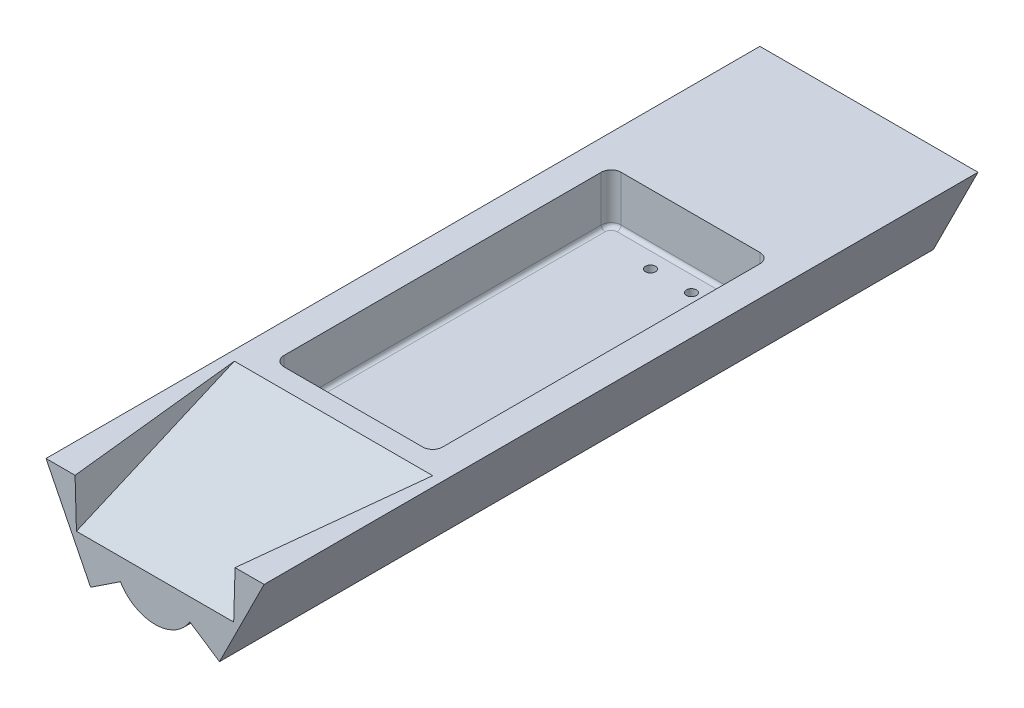
SolidWorks part; units mm, degrees
ref_plane "Front Plane" through (0, 0, 0) normal (0, 0, 1) x (1, 0, 0)
ref_plane "Top Plane" through (0, 0, 0) normal (0, 1, 0) x (1, 0, 0)
ref_plane "Right Plane" through (0, 0, 0) normal (1, 0, 0) x (0, 0, -1)
sketch "Sketch1" plane through (0, 0, 0) normal (0, 0, 1) x (1, 0, 0)
  line L6 (-279.4, 228.6) -> (279.4, 228.6)
  line L9 (0, 0) -> (0, 228.6) construction
  line L15 (-279.4, 228.6) -> (-165.1, 0)
  line L16 (-165.1, 0) -> (-88.9, 50.4)
  line L18 (165.1, 0) -> (279.4, 228.6)
  line L19 (165.1, 0) -> (88.9, 50.4)
  arc A0 (-88.9, 50.4) -> (88.9, 50.4) centre (0, 103.6049) ccw
  point P4 (88.9, 50.4)
  dimension "D1" = 558.8
  dimension "D2" = 228.6
  dimension "D3" = 228.6
  dimension "D4" = 114.3
  dimension "D5" = 114.3
  dimension "D6" = 76.2
  dimension "D7" = 76.2
extrude "Boss-Extrude2" add sketch "Sketch1" against normal blind 1828.8
sketch "Sketch2" plane through (0, 228.6, 0) normal (0, 1, 0) x (1, 0, 0)
  line L1 (-203.2, 0) -> (203.2, 0)
  line L3 (-254, 457.2) -> (254, 457.2)
  line L6 (-254, 457.2) -> (-203.2, 0)
  line L7 (254, 457.2) -> (203.2, 0)
  line L8 (279.4, 0) -> (-279.4, 0) construction
  dimension "D1" = 508
  dimension "D2" = 457.2
  dimension "D3" = 50.8
  dimension "D4" = 50.8
ref_plane "Plane1" through (0, 98.9867, 26.5234) normal (0, 0.9659, 0.2588) x (1, 0, 0)
sketch "Sketch7" plane through (0, 98.9867, 26.5234) normal (0, 0.9659, 0.2588) x (1, 0, 0)
  line L1 (-254, 500.7873) -> (254, 500.7873)
  line L2 (-254, 500.7873) -> (-196.5534, -16.2318)
  line L3 (254, 500.7873) -> (196.5534, -16.2318)
  line L6 (-196.5534, -16.2318) -> (196.5534, -16.2318)
  dimension "D1" = 508
extrude "Cut-Extrude2" cut sketch "Sketch7" along normal through all
sketch "Sketch8" plane through (0, 228.6, 0) normal (0, 1, 0) x (1, 0, 0)
  line L0 (-279.4, 1828.8) -> (-279.4, 0) construction
  line L1 (-203.2, 508) -> (203.2, 508)
  line L2 (-203.2, 508) -> (-203.2, 1371.6)
  line L3 (-203.2, 1371.6) -> (203.2, 1371.6)
  line L4 (203.2, 508) -> (203.2, 1371.6)
  line L5 (254, 457.2) -> (-254, 457.2) construction
  dimension "D1" = 406.4
  dimension "D2" = 863.6
  dimension "D3" = 76.2
  dimension "D4" = 50.8
extrude "Cut-Extrude5" cut sketch "Sketch8" against normal blind 127
fillet "Fillet1" radius 10 4 edges at (0, 101.6, -1371.6) (203.2, 101.6, -939.8) (0, 101.6, -508) (-203.2, 101.6, -939.8)
fillet "Fillet2" radius 25.4 8 edges at (200.2711, 104.5289, -510.9289) (-200.2711, 104.5289, -510.9289) (-203.2, 170.1, -508) (203.2, 170.1, -508) (-200.2711, 104.5289, -1368.6711) (200.2711, 104.5289, -1368.6711) (203.2, 170.1, -1371.6) (-203.2, 170.1, -1371.6)
sketch "Sketch9" plane through (0, 101.6, 0) normal (0, 1, 0) x (1, 0, 0)
  line L0 (0, 1371.6) -> (0, 508) construction
  line L1 (177.8, 1371.6) -> (-177.8, 1371.6) construction
  line L2 (-177.8, 508) -> (177.8, 508) construction
  circle A0 centre (-52.5, 1321.6) radius 12.7
  circle A1 centre (52.5, 1321.6) radius 12.7
  circle A2 centre (0, 571.6) radius 10
  dimension "D1" = 25.4
  dimension "D3" = 50
  dimension "D4" = 20
  dimension "D5" = 750
  dimension "D2" = 52.5
extrude "Cut-Extrude6" cut sketch "Sketch9" against normal through all
